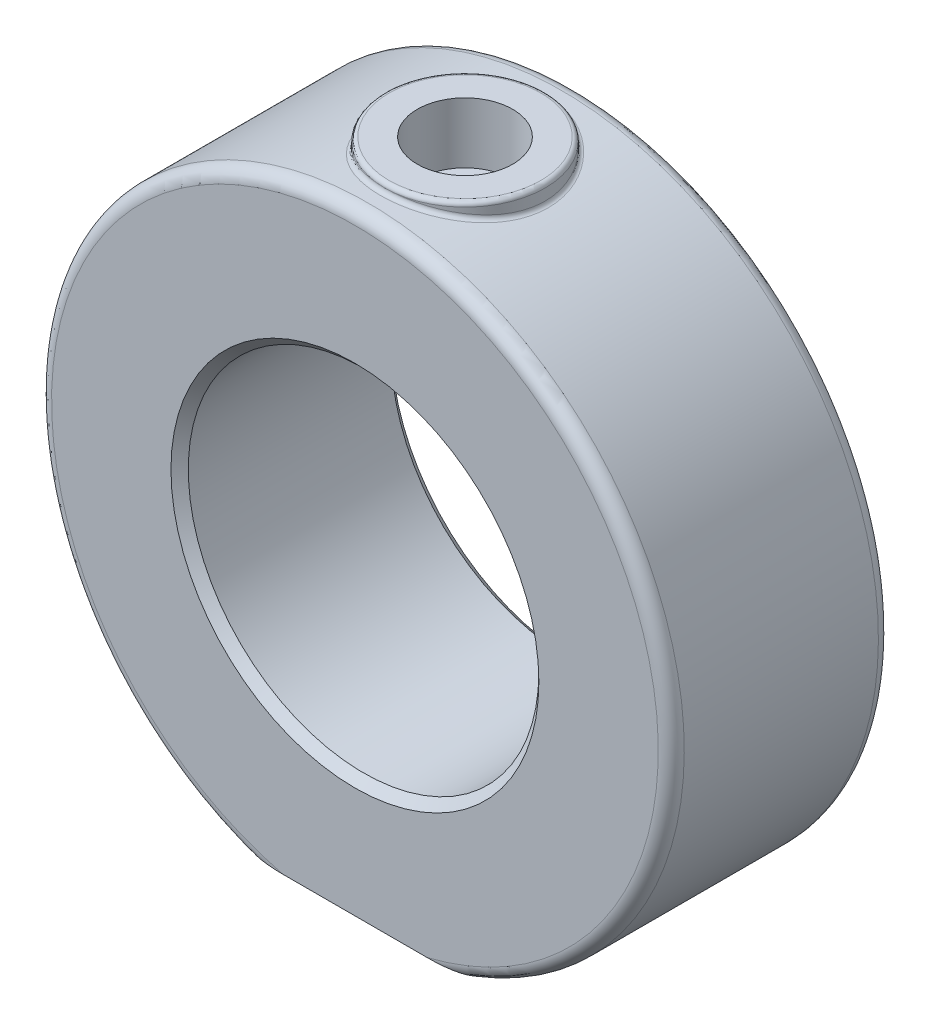
SolidWorks part; units mm, degrees
ref_plane "Płaszczyzna przednia" through (0, 0, 0) normal (0, 0, 1) x (1, 0, 0)
ref_plane "Płaszczyzna górna" through (0, 0, 0) normal (0, 1, 0) x (1, 0, 0)
ref_plane "Płaszczyzna prawa" through (0, 0, 0) normal (1, 0, 0) x (0, 0, -1)
sketch "Szkic1" plane through (0, 0, 0) normal (0, 0, 1) x (1, 0, 0)
  circle A0 centre (0, 0) radius 73
  circle A1 centre (0, 0) radius 40.45
  dimension "D1" = 146
  dimension "D2" = 80.9
extrude "Dodanie-wyciągnięcie1" add sketch "Szkic1" along normal blind 50.8
fillet "Zaokrąglenie1" radius 3 2 edges at (73, 0, 0) (73, 0, 50.8)
ref_plane "Płaszczyzna1" through (0, 75, 0) normal (0, 1, 0) x (1, 0, 0)
sketch "Szkic2" plane through (0, 75, 0) normal (0, 1, 0) x (1, 0, 0)
  line L0 (0, 0) -> (0, -25.4) construction
  circle A0 centre (0, -25.4) radius 18.5
  dimension "D1" = 37
  dimension "D2" = 25.4
extrude "Dodanie-wyciągnięcie2" add sketch "Szkic2" against normal up to surface (2 mm away) up to face at (73, 0, 3)
fillet "Zaokrąglenie2" radius 1 2 edges at (0, 75, 43.9) (-3.6011, 72.9111, 7.2539)
sketch "Szkic3" plane through (0, 75, 0) normal (0, 1, 0) x (1, 0, 0)
  circle A0 centre (0, -25.4) radius 11
  dimension "D1" = 22
extrude "Wytnij-wyciągnięcie1" cut sketch "Szkic3" against normal blind 14
sketch "Szkic4" plane through (0, 61, 0) normal (0, 1, 0) x (1, 0, 0)
  circle A0 centre (0, -25.4) radius 4.5
  dimension "D1" = 9
extrude "Wytnij-wyciągnięcie2" cut sketch "Szkic4" against normal blind 32
ref_plane "Płaszczyzna2" through (0, -68, 0) normal (0, 1, 0) x (1, 0, 0)
sketch "Szkic5" plane through (0, -68, 0) normal (0, 1, 0) x (1, 0, 0)
  line L1 (-51.2275, -81.7329) -> (51.2275, -81.7329)
  line L2 (-51.2275, -81.7329) -> (-51.2275, 30.9329)
  line L3 (-51.2275, 30.9329) -> (51.2275, 30.9329)
  line L4 (51.2275, -81.7329) -> (51.2275, 30.9329)
  line L5 (-51.2275, -81.7329) -> (51.2275, 30.9329) construction
  line L6 (-51.2275, 30.9329) -> (51.2275, -81.7329) construction
  point P0 (0, -25.4)
extrude "Wytnij-wyciągnięcie3" cut sketch "Szkic5" against normal blind 32
sketch "Szkic6" plane through (0, -68, 0) normal (0, -1, 0) x (1, 0, 0)
  circle A0 centre (0, 25.4) radius 5
  point P2 (0, 0)
  point P4 (0, 0)
  dimension "D1" = 10
  dimension "D2" = 25.4
extrude "Wytnij-wyciągnięcie4" cut sketch "Szkic6" against normal blind 5
chamfer "Sfazowanie1" distance 2 angle 45 2 edges at (40.45, 0, 0) (40.45, 0, 50.8)
ref_plane "Płaszczyzna3" through (-68, 0, 0) normal (1, 0, 0) x (0, 0, -1)
sketch "Szkic7" plane through (-68, 0, 0) normal (1, 0, 0) x (0, 0, -1)
  circle A0 centre (-25.4, -32) radius 18
  dimension "D1" = 36
  dimension "D2" = 32
  dimension "D3" = 25.4
extrude "Dodanie-wyciągnięcie3" add sketch "Szkic7" along normal up to next
fillet "Zaokrąglenie3" radius 1 3 edges at (-53.2439, -49.9408, 23.9419) (-68, -50, 25.4) (-68, -26.5518, 25.4)
